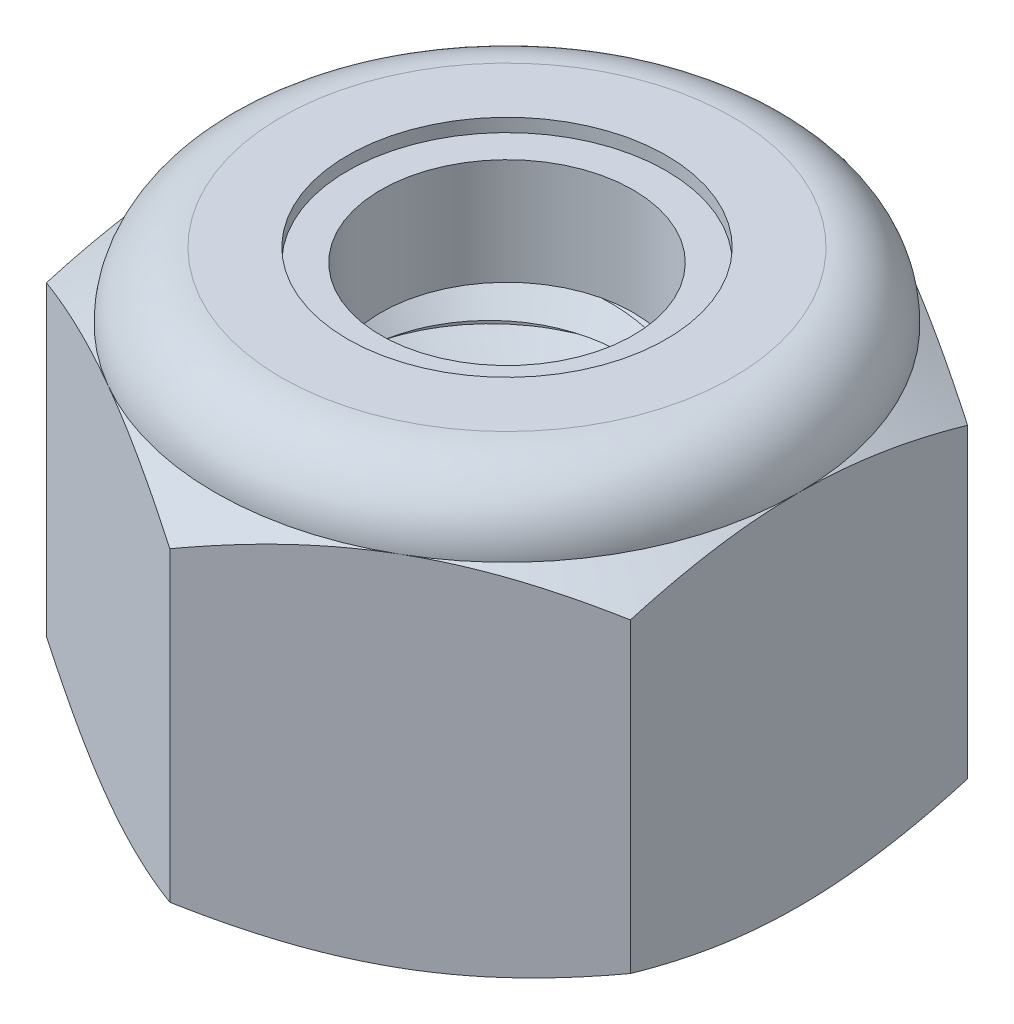
SolidWorks part; units mm, degrees
ref_plane "Front" through (0, 0, 0) normal (0, 0, 1) x (1, 0, 0)
ref_plane "Top" through (0, 0, 0) normal (0, 1, 0) x (1, 0, 0)
ref_plane "Right" through (0, 0, 0) normal (1, 0, 0) x (0, 0, -1)
sketch "Sketch1" plane through (0, 0, 0) normal (0, 1, 0) x (1, 0, 0)
  line L1 (0, 3.1754) -> (-2.75, 1.5877) construction
  line L2 (-2.75, 1.5877) -> (-2.75, -1.5877) construction
  line L3 (-2.75, -1.5877) -> (0, -3.1754) construction
  line L4 (0, -3.1754) -> (2.75, -1.5877) construction
  line L5 (2.75, -1.5877) -> (2.75, 1.5877) construction
  line L6 (2.75, 1.5877) -> (0, 3.1754) construction
  circle A0 centre (0, 0) radius 2.75 construction
  circle A1 centre (0, 0) radius 1.5 construction
  point P11 (0, -1.5)
  point P12 (0, 0)
  dimension "Thread Dia" = 3
  dimension "Width" = 5.5
sketch "Sketch2" plane through (0, 0, 0) normal (1, 0, 0) x (0, 0, -1)
  line L0 (-1.5, -2) -> (-1.5, 2) construction
  line L1 (0, 0) -> (0, 2) construction
  line L2 (0, 2) -> (-1.5, 2) construction
  line L3 (-1.5541, -1.9687) -> (-1.1211, -2.2188) construction
  line L4 (-1.1211, -2.2188) -> (-1.5541, -2.4687) construction
  line L5 (-1.5541, -2.4687) -> (-1.5541, -1.9687) construction
  line L6 (-1.1752, -2.1875) -> (-1.1752, -2.25) construction
  line L7 (-1.5271, -2.2188) -> (-1.5271, -1.9844) construction
  line L8 (-1.5, -2) -> (-1.5, -2.4375) construction
  line L9 (-1.5541, -2.2187) -> (-1.5, -2.2187) construction
  line L10 (-1.1752, -2.2187) -> (-1.1211, -2.2188) construction
  line L11 (-1.5271, -2.2188) -> (-1.5271, -2.4531) construction
  line L12 (-1.1875, 0.875) -> (-1.1875, 1.875) construction
  line L13 (-1.1875, 1.875) -> (-1.5, 1.875) construction
  line L14 (-1.5, 1.875) -> (-1.5, 0.875) construction
  line L15 (-1.5, 0.875) -> (-1.1875, 0.875) construction
  point P6 (-1.5, 0)
  point P25 (-1.1875, 1.875)
  dimension "Height" = 4
  dimension "Pitch" = 0.5
  dimension "D2" = 0.0625
  dimension "D1" = 0.3125
  dimension "D3" = 1
  dimension "D4" = 0.125
sketch "Sketch3" plane through (0, 0, 0) normal (0, 1, 0) x (1, 0, 0)
  line L0 (0, 3.1754) -> (2.75, 1.5877)
  line L1 (2.75, 1.5877) -> (2.75, -1.5877)
  line L2 (2.75, -1.5877) -> (0, -3.1754)
  line L3 (0, -3.1754) -> (-2.75, -1.5877)
  line L4 (-2.75, -1.5877) -> (-2.75, 1.5877)
  line L5 (-2.75, 1.5877) -> (0, 3.1754)
sketch "Sketch7" plane through (0, 0, 0) normal (0, 1, 0) x (1, 0, 0)
  circle A0 centre (0, 0) radius 2.75 construction
  circle A1 centre (0, 0) radius 2.75
extrude "Boss-Extrude2" add sketch "Sketch3" along normal up to vertex (-2 mm away) and the other way up to vertex (2 mm away) up to point (0, -2, 1.5) other way up to point (0, -2, 1.5)
sketch "Sketch4" plane through (0, 0, 0) normal (0, 1, 0) x (1, 0, 0)
  circle A0 centre (0, 0) radius 1.5
  circle A1 centre (0, 0) radius 1.5 construction
extrude "Cut-Extrude4" cut sketch "Sketch4" along normal through all both and the other way through all
sketch "Sketch6" plane through (0, 0, 0) normal (1, 0, 0) x (0, 0, -1)
  line L0 (2.75, -2) -> (2.75, 2) construction
  line L7 (2.75, 2) -> (2.75, 1.375) construction
  line L8 (2.75, 2) -> (2.125, 2) construction
  line L11 (2.75, 1.375) -> (3.1754, 1.375)
  line L13 (3.1754, 1.375) -> (3.1754, 2)
  line L14 (3.1754, 2) -> (2.125, 2)
  arc A1 (2.75, 1.375) -> (2.125, 2) centre (2.125, 1.375) ccw
  point P15 (2.75, 0)
  dimension "D1" = 0.625
revolve "Cut-Revolve1" cut sketch "Sketch6" angle 360 about axis through (0, 2, 0) along (0, -1, 0)
extrude "Cut-Extrude5" cut sketch "Sketch7" against normal through all draft 60 from surface flip side to cut starting at face at (0, 1.375, -2.769)
sketch "Sketch19" plane through (0, -2, 0) normal (0, -1, 0) x (1, 0, 0)
  circle A0 centre (0, 0) radius 2.75 construction
  circle A1 centre (0, 0) radius 2.75
extrude "Cut-Extrude6" cut sketch "Sketch19" against normal through all draft 60 flip side to cut
chamfer "Chamfer1" distance 0.1875 angle 45 1 edges at (0, -2, 1.5)
sketch "Sketch24" plane through (0, 0, 0) normal (1, 0, 0) x (0, 0, -1)
  line L0 (-1.5, 1.875) -> (-1.1875, 1.875)
  line L1 (-1.1875, 1.875) -> (-1.1875, 0.875)
  line L2 (-1.1875, 0.875) -> (-1.5, 0.875)
  line L3 (-1.5, 0.875) -> (-1.5, 1.875)
revolve "Revolve1" add sketch "Sketch24" angle 360 about L1
ref_plane "Contact Plane 1" through (0, 2, 0) normal (0, 1, 0) x (1, 0, 0)
ref_plane "Contact Plane 2" through (0, -2, 0) normal (0, -1, 0) x (-1, 0, 0)
sketch "Sketch5" plane through (0, -2, 0) normal (0, 1, 0) x (1, 0, 0)
  circle A1 centre (0, 0) radius 1.5
  circle A2 centre (0, 0) radius 1.5 construction
curve "Helix/Spiral1" pitch 0.5 height 4 radius 1.5 centre (0, -2, 0) axis (0, 1, 0) start towards (0, 0, 1)
sketch "Sketch21" plane through (0, 0, 0) normal (1, 0, 0) x (0, 0, -1)
  line L0 (-1.5271, -1.9844) -> (-1.5271, -2.4531)
  line L1 (-1.5271, -2.4531) -> (-1.1752, -2.25)
  line L2 (-1.1752, -2.25) -> (-1.1752, -2.1875)
  line L3 (-1.1752, -2.1875) -> (-1.5271, -1.9844)
sweep "Sweep1" add profiles "Sketch21" path "Helix/Spiral1"
sketch "Sketch23" plane through (0, 0.875, 0) normal (0, 1, 0) x (1, 0, 0)
  line L0 (0, 0) -> (0, -1.5) construction
  circle A1 centre (0, 0) radius 1.5541
extrude "Cut-Extrude8" cut sketch "Sketch23" along normal through all and the other way through all draft 45
combine bodies "Combine1" operation type add bodies to combine 147 143
sketch "Sketch30" plane through (0, -2, 0) normal (0, -1, 0) x (1, 0, 0)
  circle A0 centre (0, 0) radius 1.6875 construction
  circle A1 centre (0, 0) radius 1.6875
extrude "Cut-Extrude12" cut sketch "Sketch30" along normal through all and the other way through all draft 45
equation "\"D2@Sketch2\" = \"Pitch@Sketch2\" / 8"
equation "\"D1@Sketch2\"=\"Pitch@Sketch2\"*.625"
equation "\"D3@Sketch2\"=\"Height@Sketch2\"/4"
equation "\"D4@Sketch2\"=\"Pitch@Sketch2\"/4"
equation "\"D4@Helix/Spiral1\"=\"Pitch@Sketch2\""
equation "\"D3@Helix/Spiral1\"=\"Height@Sketch2\""
equation "\"D1@Sketch6\"=\"Pitch@Sketch2\"*1.25"
equation "\"D1@Chamfer1\"=\"Pitch@Sketch2\"*.375"
